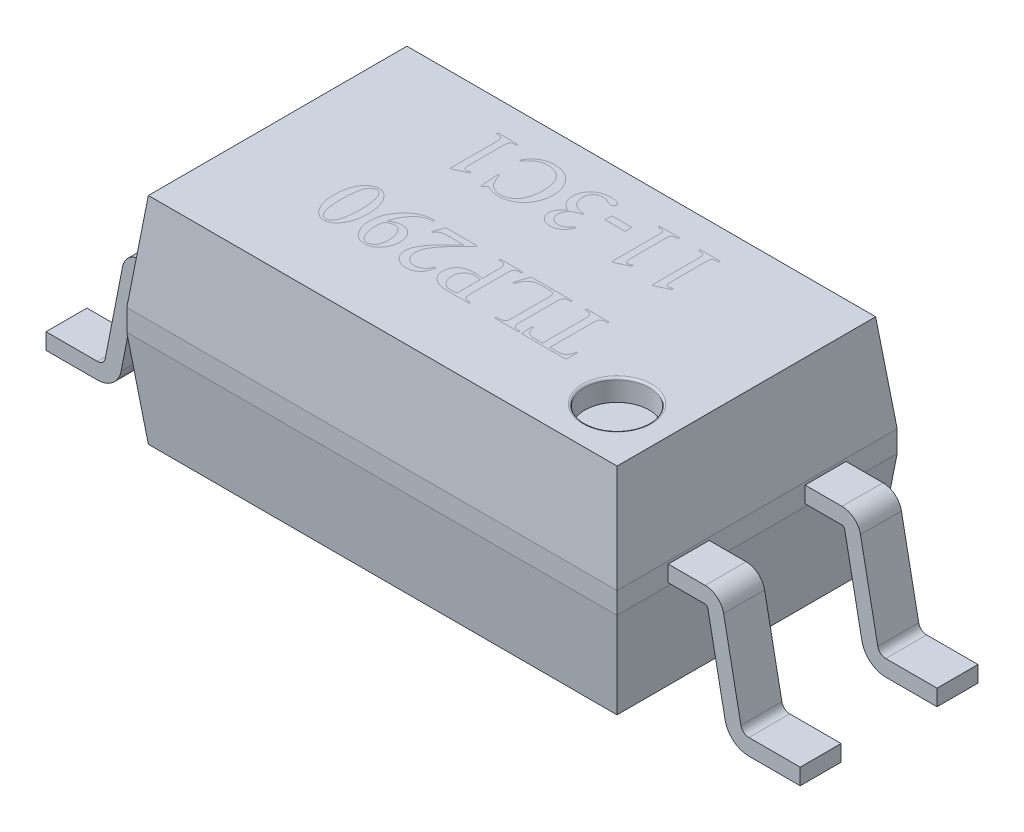
SolidWorks part; units mm, degrees
material "ABS"
ref_plane "Спереди" through (0, 0, 0) normal (0, 0, 1) x (1, 0, 0)
ref_plane "Сверху" through (0, 0, 0) normal (0, 1, 0) x (1, 0, 0)
ref_plane "Справа" through (0, 0, 0) normal (1, 0, 0) x (0, 0, -1)
sketch "Эскиз1" plane through (0, 0, 0) normal (0, 1, 0) x (1, 0, 0)
  line L1 (-2.275, 1.3) -> (2.275, 1.3)
  line L2 (-2.275, 1.3) -> (-2.275, -1.3)
  line L3 (-2.275, -1.3) -> (2.275, -1.3)
  line L4 (2.275, 1.3) -> (2.275, -1.3)
  dimension "D1" = 4.55
  dimension "D2" = 2.275
  dimension "D3" = 2.6
  dimension "D4" = 1.3
extrude "Вытянуть1" add sketch "Эскиз1" along normal blind 1 and the other way blind 1
chamfer "Фаска1" distance 0.9 distance2 0.1 4 edges at (0, 1, -1.3) (2.275, 1, 0) (0, 1, 1.3) (-2.275, 1, 0) first distance on face at (0, 0, -1.3) first distance on face at (2.275, 0, 0) first distance on face at (0, 0, 1.3) first distance on face at (-2.275, 0, 0)
chamfer "Фаска2" distance 0.1 distance2 0.9 4 edges at (0, -1, 1.3) (2.275, -1, 0) (0, -1, -1.3) (-2.275, -1, 0) first distance on face at (0, -1, 0)
ref_plane "Плоскость1" through (0, 0, 0.635) normal (0, 0, 1) x (1, 0, 0)
ref_plane "Плоскость2" through (0, 0, -0.635) normal (0, 0, 1) x (1, 0, 0)
sketch "Эскиз2" plane through (0, 0, 0.635) normal (0, 0, 1) x (1, 0, 0)
  line L0 (2.275, 0) -> (2.6177, 0)
  line L1 (2.275, -0.1) -> (2.275, 0.1) construction
  line L2 (2.7158, -0.0808) -> (2.8762, -0.8989)
  line L3 (3.5, -1.02) -> (3.0234, -1.02)
  line L4 (2.7, 0) -> (2.7, -0.6259) construction
  line L5 (0, 0) -> (0, 2.7586) construction
  line L6 (2.175, -1) -> (-2.175, -1) construction
  arc A0 (2.7158, -0.0808) -> (2.6177, 0) centre (2.6177, -0.1) ccw
  arc A1 (3.0234, -1.02) -> (2.8762, -0.8989) centre (3.0234, -0.87) cw
  point P17 (2.9, -1.02)
  dimension "D2" = 0.2
  dimension "D4" = 0.1
  dimension "D3" = 0.02
  dimension "D6" = 0.15
  dimension "D1" = 0.6
  dimension "D5" = 0.425
ref_plane "Плоскость3" through (3.5, -1.02, 0.635) normal (-1, 0, 0) x (0, 0, 1)
sketch "Эскиз3" plane through (3.5, -1.02, 0.635) normal (-1, 0, 0) x (0, 0, 1)
  line L0 (0, 0) -> (0, -0.3154) construction
  line L1 (-0.19, 0.075) -> (0.19, 0.075)
  line L2 (-0.19, 0.075) -> (-0.19, -0.075)
  line L3 (-0.19, -0.075) -> (0.19, -0.075)
  line L4 (0.19, 0.075) -> (0.19, -0.075)
  line L5 (0, -199998.98) -> (0, 200003.7786) construction
  line L6 (0, 0) -> (-0.313, 0) construction
  dimension "D1" = 0.38
  dimension "D3" = 0.15
sweep "По траектории2" add profiles "Эскиз3" path "Эскиз2"
pattern_linear "Линейный массив1" count 2 spacing 1.27 along (0, 0, -1) of "По траектории2"
mirror "Зеркальное отражение2" about plane through (0, 0, 0) normal (1, 0, 0) of "Линейный массив1"
sketch "Эскиз4" plane through (0, 1, 0) normal (0, 1, 0) x (1, 0, 0)
  line L0 (2.275, -1.3) -> (-2.275, -1.3) construction
  circle A0 centre (1.675, -0.7) radius 0.3
  dimension "D1" = 0.6
  dimension "D2" = 0.6
  dimension "D3" = 1.675
extrude "Вытянуть2" cut sketch "Эскиз4" against normal blind 0.2
fillet "Скругление1" radius 0.02 1 edges at (1.675, 1, 1)
sketch "Эскиз5" plane through (0, 1, 0) normal (0, 1, 0) x (-1, 0, 0)
  text T0 "TLP290\r\n11-3C1" font "Times New Roman" height 0.5
wrap "Переносить слова1" sketch "Эскиз5" wrap type scribe source sketch "Эскиз5" face at (1.675, 1, 1.02)
